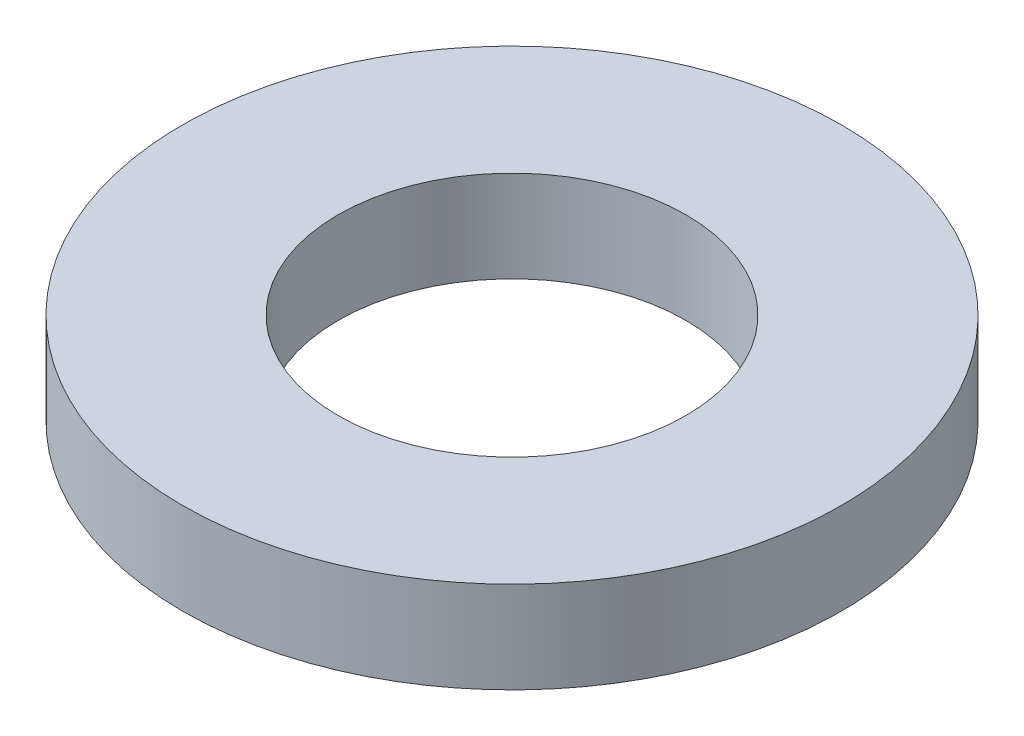
SolidWorks part; units mm, degrees
ref_plane "Front Plane" through (0, 0, 0) normal (0, 0, 1) x (1, 0, 0)
ref_plane "Top Plane" through (0, 0, 0) normal (0, 1, 0) x (1, 0, 0)
ref_plane "Right Plane" through (0, 0, 0) normal (1, 0, 0) x (0, 0, -1)
sketch "Sketch1" plane through (0, 0, 0) normal (0, 1, 0) x (1, 0, 0)
  circle A0 centre (0, 0) radius 90
  dimension "FLANGE_OD" = 180
extrude "Boss-Extrude1" add sketch "Sketch1" along normal blind 25
sketch "Sketch2" plane through (0, 0, 0) normal (0, 1, 0) x (1, 0, 0)
  circle A0 centre (0, 0) radius 47.5
  dimension "BORE_D" = 95
extrude "Cut-Extrude1" cut sketch "Sketch2" along normal through all
sketch "Sketch3" plane through (0, 25, 0) normal (0, 1, 0) x (1, 0, 0)
  circle A0 centre (0, 0) radius 27.1239 construction
  circle A1 centre (-27.1239, 0) radius 3.1038
  dimension "BOLT_D" = 6.2075
  dimension "BOLT_PCD" = 54.2477
extrude "Cut-Extrude2" cut sketch "Sketch3" against normal blind 24.2539 rebuild error yes
pattern_circular "CirPattern1" count 3 over 360 rebuild error yes
